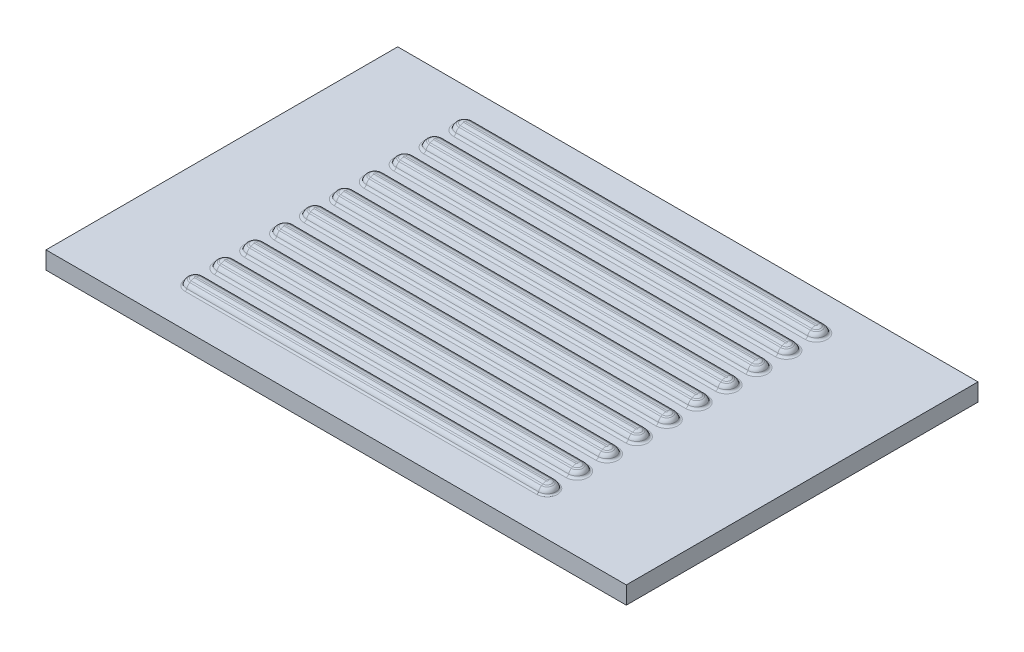
SolidWorks part; units mm, degrees
ref_plane "Front Plane" through (0, 0, 0) normal (0, 0, 1) x (1, 0, 0)
ref_plane "Top Plane" through (0, 0, 0) normal (0, 1, 0) x (1, 0, 0)
ref_plane "Right Plane" through (0, 0, 0) normal (1, 0, 0) x (0, 0, -1)
sketch "Sketch1" plane through (0, 0, 0) normal (0, 1, 0) x (1, 0, 0)
  line L1 (-15000, 10000) -> (15000, 10000)
  line L2 (-15000, 10000) -> (-15000, -10000)
  line L3 (-15000, -10000) -> (15000, -10000)
  line L4 (15000, 10000) -> (15000, -10000)
  line L5 (-15000, 10000) -> (15000, -10000) construction
  line L6 (-15000, -10000) -> (15000, 10000) construction
  point P0 (0, 0)
  dimension "D1" = 20000
  dimension "D2" = 30000
extrude "Boss-Extrude1" add sketch "Sketch1" against normal blind 1000
sketch "Sketch4" plane through (0, 0, 0) normal (0, 1, 0) x (1, 0, 0)
  line L1 (-15000, 10000) -> (-18000, 10000)
  line L2 (-15000, 10000) -> (-15000, -10000)
  line L3 (-15000, -10000) -> (-18000, -10000)
  line L4 (-18000, 10000) -> (-18000, -10000)
  point P5 (-15000, -10000)
  dimension "D1" = 3000
extrude "Boss-Extrude3" add sketch "Sketch4" against normal blind 1000
sketch "Sketch3" plane through (0, 0, 0) normal (0, 1, 0) x (1, 0, 0)
  line L0 (-12000, -7500) -> (8000, -7500) construction
  line L1 (-12000, -7000) -> (8000, -7000)
  line L2 (-12000, -8000) -> (8000, -8000)
  line L3 (-18000, -10000) -> (15000, -10000) construction
  line L6 (-18000, 10000) -> (-18000, -10000) construction
  arc A0 (-12000, -7000) -> (-12000, -8000) centre (-12000, -7500) ccw
  arc A1 (8000, -8000) -> (8000, -7000) centre (8000, -7500) ccw
  point P2 (-2000, -7500)
  dimension "D4" = 6000
  dimension "D1" = 1000
  dimension "D2" = 20000
  dimension "D3" = 2500
extrude "Boss-Extrude2" add sketch "Sketch3" along normal blind 400
chamfer "Chamfer1" distance 200 angle 60 4 edges at (-2000, 400, 7000) (8500, 400, 7500) (-2000, 400, 8000) (-12500, 400, 7500) first distance on face at (-2000, 200, 7000) first distance on face at (8250, 200, 7500) first distance on face at (-2000, 200, 8000) first distance on face at (-12250, 200, 7500)
fillet "Fillet3" radius 400 4 edges at (-2000, 400, 7653.5898) (-12153.5898, 400, 7500) (-2000, 400, 7346.4102) (8153.5898, 400, 7500)
fillet "Fillet4" radius 350 4 edges at (-12500, 200, 7500) (-2000, 200, 8000) (8500, 200, 7500) (-2000, 200, 7000)
fillet "Fillet2" radius 100 4 edges at (8500, 0, 7500) (-2000, 0, 7000) (-12500, 0, 7500) (-2000, 0, 8000)
pattern_linear "LPattern3" count 10 spacing 1700 along (0, 0, -1) of "Boss-Extrude2", "Chamfer1", "Fillet3", "Fillet4"
fillet "Fillet5" radius 150 4 edges at (-2000, 0, 6300) (-12500, 0, 5800) (-2000, 0, 5300) (8500, 0, 5800)
fillet "Fillet6" radius 150 4 edges at (-2000, 0, 4600) (-12500, 0, 4100) (-2000, 0, 3600) (8500, 0, 4100)
fillet "Fillet7" radius 150 4 edges at (-2000, 0, 2900) (-12500, 0, 2400) (-2000, 0, 1900) (8500, 0, 2400)
fillet "Fillet8" radius 150 4 edges at (-2000, 0, 1200) (-12500, 0, 700) (-2000, 0, 200) (8500, 0, 700)
fillet "Fillet9" radius 150 4 edges at (8500, 0, -1000) (-2000, 0, -500) (-12500, 0, -1000) (-2000, 0, -1500)
fillet "Fillet10" radius 150 4 edges at (-2000, 0, -2200) (-12500, 0, -2700) (-2000, 0, -3200) (8500, 0, -2700)
fillet "Fillet11" radius 150 4 edges at (8500, 0, -4400) (-2000, 0, -4900) (-12500, 0, -4400) (-2000, 0, -3900)
fillet "Fillet12" radius 150 4 edges at (8500, 0, -6100) (-2000, 0, -6600) (-12500, 0, -6100) (-2000, 0, -5600)
fillet "Fillet13" radius 150 4 edges at (8500, 0, -7800) (-2000, 0, -8300) (-12500, 0, -7800) (-2000, 0, -7300)
